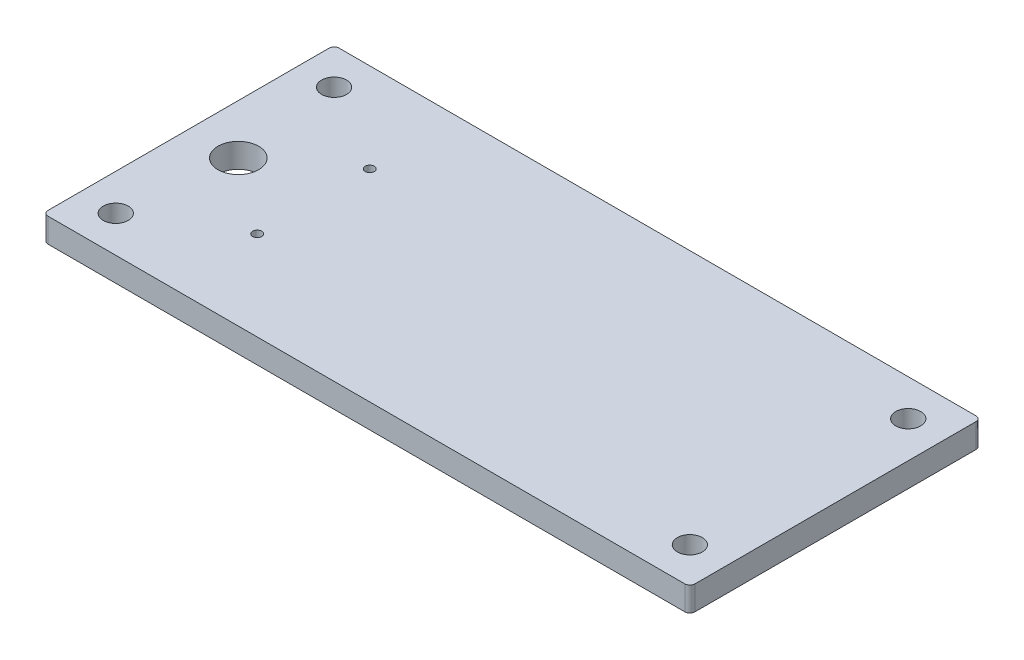
SolidWorks part; units mm, degrees
material "ABS"
ref_plane "Front Plane" through (0, 0, 0) normal (0, 0, 1) x (1, 0, 0)
ref_plane "Top Plane" through (0, 0, 0) normal (0, 1, 0) x (1, 0, 0)
ref_plane "Right Plane" through (0, 0, 0) normal (1, 0, 0) x (0, 0, -1)
sketch "Sketch1" plane through (0, 0, 0) normal (0, 1, 0) x (1, 0, 0)
  line L1 (-127, -57.15) -> (127, -57.15)
  line L2 (-127, -57.15) -> (-127, 57.15)
  line L3 (-127, 57.15) -> (127, 57.15)
  line L4 (127, -57.15) -> (127, 57.15)
  line L5 (-127, -57.15) -> (127, 57.15) construction
  line L6 (-127, 57.15) -> (127, -57.15) construction
  point P0 (0, 0)
  dimension "D1" = 254
  dimension "D2" = 114.3
extrude "Boss-Extrude1" add sketch "Sketch1" along normal blind 9.525
fillet "Fillet1" radius 2 4 edges at (-127, 4.7625, -57.15) (127, 4.7625, -57.15) (-127, 4.7625, 57.15) (127, 4.7625, 57.15)
sketch "Sketch8" plane through (0, 9.525, 0) normal (0, 1, 0) x (1, 0, 0)
  point P0 (112.7125, 42.8625)
  point P1 (112.7125, -42.8675)
  point P3 (-112.7175, 42.8625)
  point P5 (-112.7175, -42.8675)
hole_wizard "3/8 Clearance Hole1" positions "Sketch8" profile "Sketch9" hole size "3/8" standard "ANSI Inch"
sketch "Sketch9" plane through (112.7125, 9.525, -42.8625) normal (1, 0, 0) x (0, 0, 1)
  line L0 (0, 0) -> (0, 12.9455)
  line L1 (0, 12.9455) -> (4.9022, 10)
  line L2 (4.9022, 10) -> (4.9022, 0)
  line L5 (4.9022, 0) -> (0, 0)
  line L10 (0, 12.9455) -> (-4.9022, 10) construction
  line L11 (0, -6.35) -> (0, 107.95) construction
  dimension "Hole Dia." = 9.8044
  dimension "Hole Depth" = 10
  dimension "Drill Angle" = 118
sketch "Sketch10" plane through (0, 9.525, 0) normal (0, 1, 0) x (1, 0, 0)
  line L0 (0, 0) -> (-127, 0) construction
  line L1 (-127, 55.15) -> (-127, -55.15) construction
  circle A0 centre (-107.475, 0) radius 8
  dimension "D1" = 16
  dimension "D2" = 19.525
extrude "Cut-Extrude2" cut sketch "Sketch10" against normal through all
sketch "Sketch11" plane through (0, 9.525, 0) normal (0, 1, 0) x (1, 0, 0)
  line L0 (-127, 55.15) -> (-127, -55.15) construction
  line L1 (-88.9, 27.15) -> (-67, 27.15) construction
  line L2 (-88.9, 27.15) -> (-88.9, -27.15) construction
  line L3 (-88.9, -27.15) -> (-67, -27.15) construction
  line L4 (-67, 27.15) -> (-67, -27.15) construction
  point P5 (-77.95, -22.1)
  point P6 (-77.95, 22.1)
  point P25 (-88.9, 0)
  dimension "D1" = 54.3
  dimension "D2" = 21.9
  dimension "D3" = 10.95
  dimension "D4" = 5.05
  dimension "D5" = 44.2
  dimension "D6" = 38.1
  dimension "D7" = 10.95
hole_wizard "M3 Clearance Hole1" positions "Sketch11" profile "Sketch12" hole size "M3" standard "ANSI Metric"
sketch "Sketch12" plane through (-77.95, 9.525, -22.1) normal (1, 0, 0) x (0, 0, 1)
  line L0 (0, 0) -> (0, 11.0815)
  line L1 (0, 11.0815) -> (1.8, 10)
  line L2 (1.8, 10) -> (1.8, 0)
  line L5 (1.8, 0) -> (0, 0)
  line L10 (0, 11.0815) -> (-1.8, 10) construction
  line L11 (0, -6.35) -> (0, 107.95) construction
  dimension "Hole Dia." = 3.6
  dimension "Hole Depth" = 10
  dimension "Drill Angle" = 118
